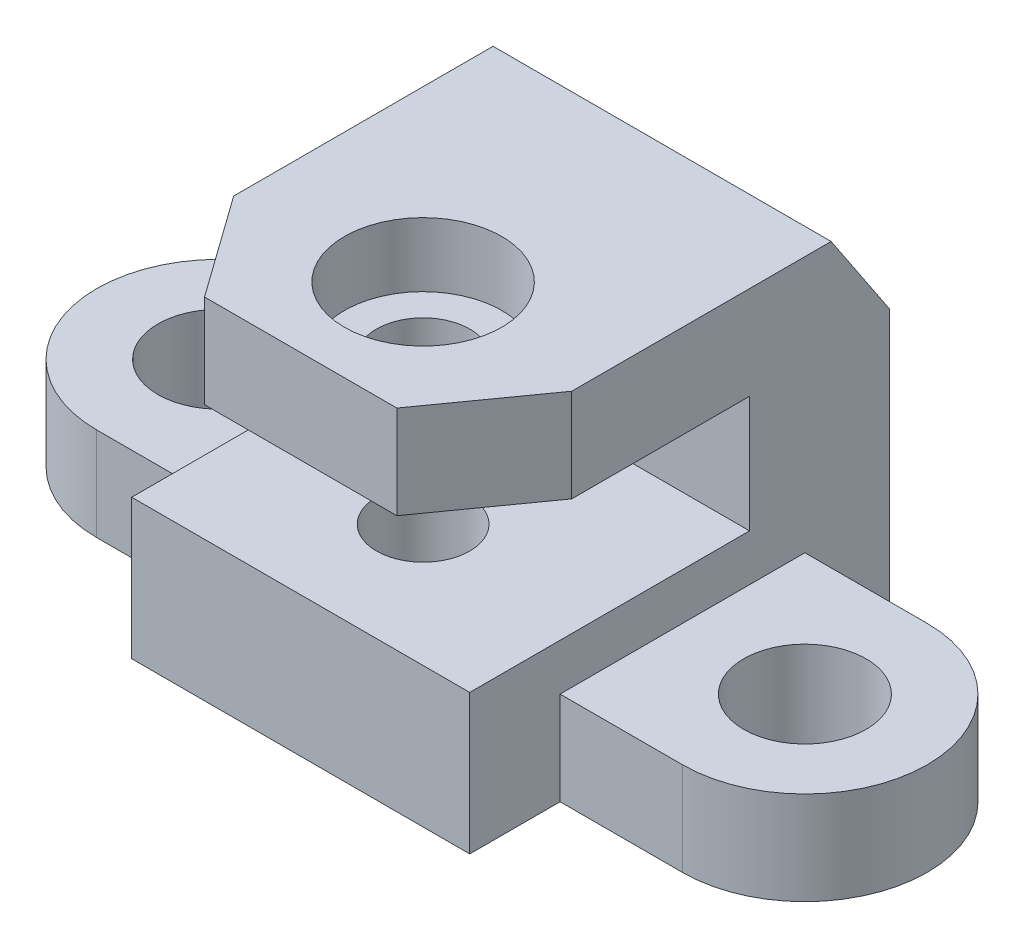
SolidWorks part; units mm, degrees
material "铜"
ref_plane "前视基准面" through (0, 0, 0) normal (0, 0, 1) x (1, 0, 0)
ref_plane "上视基准面" through (0, 0, 0) normal (0, 1, 0) x (1, 0, 0)
ref_plane "右视基准面" through (0, 0, 0) normal (1, 0, 0) x (0, 0, -1)
sketch "草图1" plane through (0, 0, 0) normal (0, 1, 0) x (1, 0, 0)
  line L1 (-58, 0) -> (58, 0)
  line L2 (-58, 0) -> (-58, 144)
  line L3 (-58, 144) -> (58, 144)
  line L4 (58, 0) -> (58, 144)
extrude "凸台-拉伸1" add sketch "草图1" along normal blind 120
sketch "草图2" plane through (0, 0, 0) normal (0, 1, 0) x (1, 0, 0)
  line L0 (-100, 114) -> (-58, 114)
  line L1 (-58, 144) -> (-58, 0) construction
  line L2 (-58, 114) -> (-58, 30)
  line L3 (-58, 30) -> (-100, 30)
  line L4 (100, 115) -> (58, 115)
  line L5 (58, 0) -> (58, 144) construction
  line L6 (58, 115) -> (58, 31)
  line L7 (58, 31) -> (100, 31)
  arc A0 (-100, 114) -> (-100, 30) centre (-100, 72) ccw
  circle A1 centre (-100, 72) radius 21
  arc A2 (100, 31) -> (100, 115) centre (100, 73) ccw
  circle A3 centre (100, 73) radius 21
extrude "凸台-拉伸3" add sketch "草图2" along normal blind 32
ref_plane "基准面1" through (0, 120, 0) normal (0, 1, 0) x (1, 0, 0)
sketch "草图4" plane through (0, 120, 0) normal (0, 1, 0) x (1, 0, 0)
  circle A0 centre (0, 42) radius 16
extrude "切除-拉伸1" cut sketch "草图4" against normal blind 120
sketch "草图5" plane through (0, 120, 0) normal (0, 1, 0) x (1, 0, 0)
  circle A0 centre (0, 42) radius 27
extrude "切除-拉伸2" cut sketch "草图5" against normal blind 22
sketch "草图13" plane through (0, 0, 0) normal (1, 0, 0) x (0, 0, -1)
  line L0 (144, 120) -> (124, 120)
  line L1 (79.2, 120) -> (-79.2, 120) construction
  line L2 (144, 120) -> (144, 0) construction
  line L3 (124, 120) -> (144, 90)
  line L4 (144, 90) -> (144, 120)
  line L6 (0, 88) -> (96, 88)
  line L7 (0, 88) -> (0, 48)
  line L8 (0, 48) -> (96, 48)
  line L9 (96, 88) -> (96, 48)
  dimension "D1" = 30
  dimension "D2" = 20
extrude "切除-拉伸6" cut sketch "草图13" against normal blind 58 and the other way blind 58
sketch "草图15" plane through (0, 120, 0) normal (0, 1, 0) x (1, 0, 0)
  line L0 (-58, 0) -> (-58, 35)
  line L1 (-58, 124) -> (-58, 0) construction
  line L2 (-58, 35) -> (-33, 0)
  line L3 (-58, 0) -> (58, 0) construction
  line L4 (-33, 0) -> (-58, 0)
  line L5 (58, 0) -> (58, 35)
  line L6 (58, 115) -> (58, 31) construction
  line L7 (58, 35) -> (33, 0)
  line L8 (33, 0) -> (58, 0)
  dimension "D1" = 25
  dimension "D2" = 35
  dimension "D3" = 25
extrude "切除-拉伸7" cut sketch "草图15" against normal blind 32
